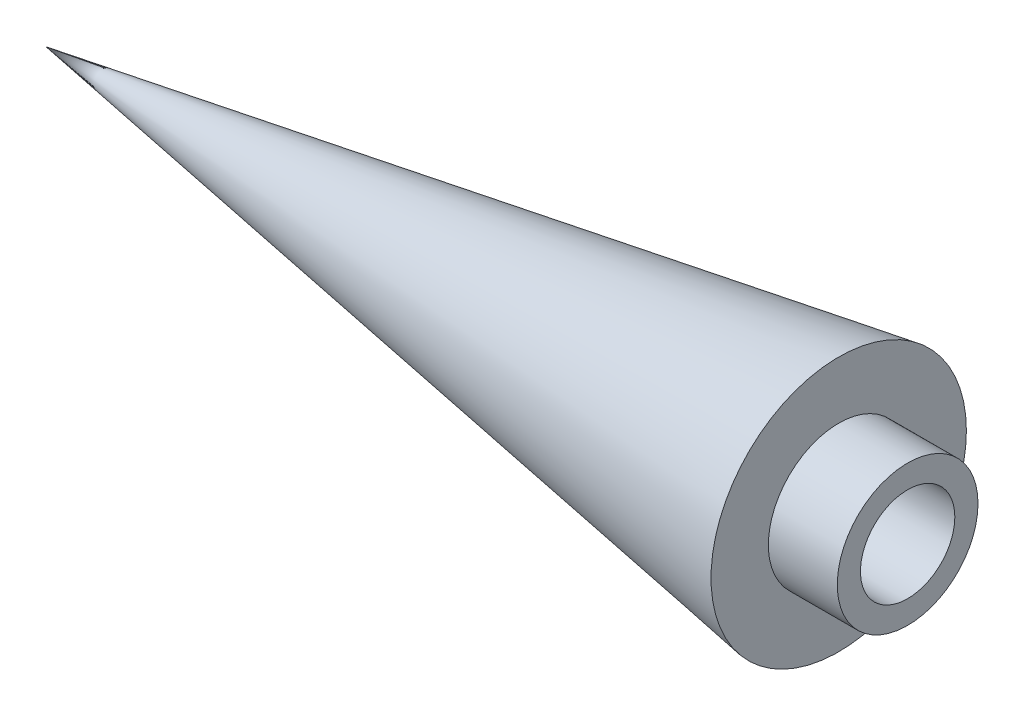
SolidWorks part; units mm, degrees
ref_plane "Płaszczyzna przednia" through (0, 0, 0) normal (0, 0, 1) x (1, 0, 0)
ref_plane "Płaszczyzna górna" through (0, 0, 0) normal (0, 1, 0) x (1, 0, 0)
ref_plane "Płaszczyzna prawa" through (0, 0, 0) normal (1, 0, 0) x (0, 0, -1)
sketch "Sketch1" plane through (0, 0, 0) normal (0, 0, 1) x (1, 0, 0)
  line L1 (0, 0) -> (0, 18.525)
  line L2 (0, 18.525) -> (-115, 0)
  line L3 (0, 0) -> (-115, 0) construction
  line L4 (0, 0) -> (-115, 0)
  dimension "D1" = 115
  dimension "D2" = 18.525
revolve "Revolve1" add sketch "Sketch1" angle 360 about L3
sketch "Sketch2" plane through (0, 0, 0) normal (1, 0, 0) x (0, 0, -1)
  circle A0 centre (0, 0) radius 3
  dimension "D1" = 6
extrude "Cut-Extrude1" cut sketch "Sketch2" against normal blind 50
sketch "Sketch3" plane through (0, 0, 0) normal (1, 0, 0) x (0, 0, -1)
  circle A0 centre (0, 0) radius 6.8454
  circle A1 centre (0, 0) radius 10.2081
extrude "Boss-Extrude1" add sketch "Sketch3" along normal blind 10
